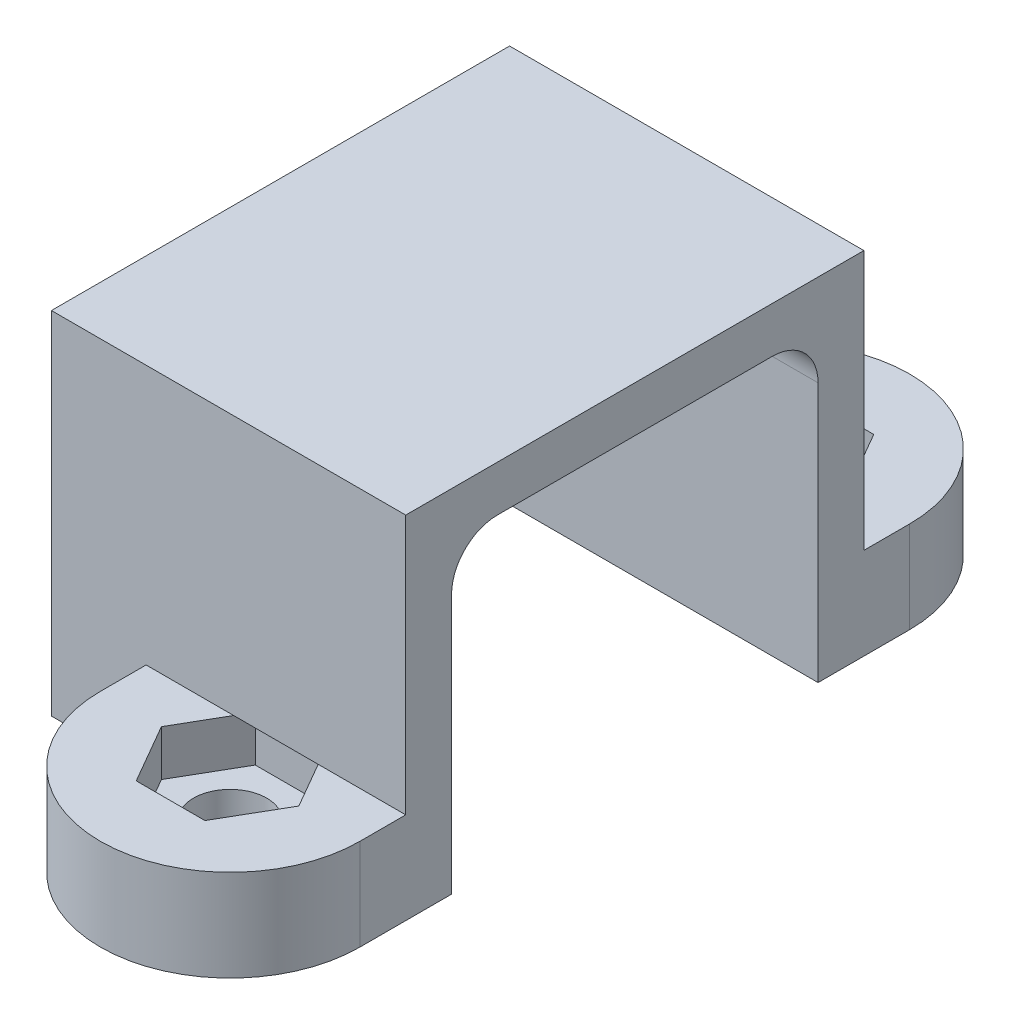
SolidWorks part; units mm, degrees
material "ABS PC"
ref_plane "Front Plane" through (0, 0, 0) normal (0, 0, 1) x (1, 0, 0)
ref_plane "Top Plane" through (0, 0, 0) normal (0, 1, 0) x (1, 0, 0)
ref_plane "Right Plane" through (0, 0, 0) normal (1, 0, 0) x (0, 0, -1)
sketch "Sketch1" plane through (0, 0, 0) normal (0, 1, 0) x (1, 0, 0)
  line L0 (0, 7.5) -> (0, -7.5) construction
  line L1 (-7.35, 0) -> (4.25, 0) construction
  line L6 (-7.35, 7.5) -> (4.25, 7.5)
  line L7 (-7.35, 7.5) -> (-7.35, -7.5)
  line L8 (-7.35, -7.5) -> (4.25, -7.5)
  line L9 (4.25, 7.5) -> (4.25, -7.5)
  line L10 (-7.35, 7.5) -> (4.25, -7.5) construction
  line L11 (-7.35, -7.5) -> (4.25, 7.5) construction
  point P3 (-1.55, 0)
  dimension "D1" = 11.6
  dimension "D2" = 15
  dimension "D3" = 4.25
extrude "body" add sketch "Sketch1" along normal blind 11.5
sketch "Sketch2" plane through (0, 0, 0) normal (0, 1, 0) x (1, 0, 0)
  line L0 (-7.35, 0) -> (4.25, 0) construction
  line L1 (-7.35, 7.5) -> (-7.35, -7.5) construction
  line L2 (4.25, -7.5) -> (4.25, 7.5) construction
  line L3 (0, 7.5) -> (0, -7.5) construction
  line L4 (4.25, 7.5) -> (-7.35, 7.5) construction
  line L5 (-7.35, -7.5) -> (4.25, -7.5) construction
  line L6 (-4.25, 9) -> (-4.25, 7.5)
  line L11 (4.25, -7.5) -> (4.25, -9)
  line L12 (-4.25, -7.5) -> (4.25, -7.5)
  line L13 (-4.25, 7.5) -> (4.25, 7.5)
  line L14 (4.25, 7.5) -> (4.25, 9)
  line L15 (-4.25, -9) -> (-4.25, -7.5)
  arc A0 (-4.25, 9) -> (4.25, 9) centre (0, 9) cw
  arc A1 (-4.25, -9) -> (4.25, -9) centre (0, -9) ccw
  dimension "D1" = 8.5
  dimension "D2" = 18
extrude "flange" add sketch "Sketch2" along normal blind 3
ref_plane "MotorFace" through (-4.05, 0, 0) normal (1, 0, 0) x (0, 0, -1)
ref_axis "AX-bolt" through (0, 3, -9) along (0, -1, 0)
ref_axis "AX-bolt2" through (0, 3, 9) along (0, -1, 0)
sketch "Sketch5" plane through (0, 0, 0) normal (0, 1, 0) x (1, 0, 0)
  line L0 (4.25, 7.5) -> (-7.35, 7.5) construction
  line L1 (2.25, 9) -> (1.125, 10.9486)
  line L2 (1.125, 10.9486) -> (-1.125, 10.9486)
  line L3 (-1.125, 10.9486) -> (-2.25, 9)
  line L4 (-2.25, 9) -> (-1.125, 7.0514)
  line L5 (-1.125, 7.0514) -> (1.125, 7.0514)
  line L6 (1.125, 7.0514) -> (2.25, 9)
  line L8 (2.25, -9) -> (1.125, -7.0514)
  line L9 (1.125, -7.0514) -> (-1.125, -7.0514)
  line L10 (-1.125, -7.0514) -> (-2.25, -9)
  line L11 (-2.25, -9) -> (-1.125, -10.9486)
  line L12 (-1.125, -10.9486) -> (1.125, -10.9486)
  line L13 (1.125, -10.9486) -> (2.25, -9)
  circle A0 centre (0, 9) radius 1.9486 construction
  circle A1 centre (0, -9) radius 1.9486 construction
  dimension "D1" = 4.5
extrude "holder-nut" cut sketch "Sketch5" against normal blind 1.5 from surface starting at face at (0, 3, -9.3125)
sketch "Sketch8" plane through (0, 0, 0) normal (0, 1, 0) x (1, 0, 0)
  circle A0 centre (0, 9) radius 1.2
  circle A1 centre (0, -9) radius 1.2
  dimension "D1" = 2.4
extrude "hole-M2" cut sketch "Sketch8" against normal through all and the other way through all
sketch "Sketch7" plane through (0, 0, 0) normal (1, 0, 0) x (0, 0, -1)
  line L0 (-9, 0) -> (9, 0) construction
  line L1 (-4.5, 10) -> (4.5, 10)
  line L2 (-6, 8.5) -> (-6, 0)
  line L3 (-6, 0) -> (6, 0)
  line L4 (6, 8.5) -> (6, 0)
  line L5 (0, 0) -> (0, 11.5) construction
  line L6 (-7.5, 11.5) -> (7.5, 11.5) construction
  line L7 (7.5, 11.5) -> (7.5, 3) construction
  arc A0 (6, 8.5) -> (4.5, 10) centre (4.5, 8.5) ccw
  arc A1 (-4.5, 10) -> (-6, 8.5) centre (-4.5, 8.5) ccw
  dimension "D3" = 1.5
  dimension "D1" = 1.5
  dimension "D2" = 1.5
extrude "fixture-motor" cut sketch "Sketch7" against normal through all both and the other way through all
sketch "Sketch9" plane through (4.25, 0, 0) normal (1, 0, 0) x (0, 0, -1)
  line L0 (-6, 8.5) -> (-6, 10)
  line L1 (-6, 10) -> (-4.5, 10)
  line L2 (4.5, 10) -> (6, 10)
  line L3 (6, 10) -> (6, 8.5)
  line L12 (6, 8.5) -> (6, 0)
  line L13 (6, 0) -> (9, 0)
  line L14 (9, 0) -> (9, 3)
  line L15 (9, 3) -> (7.5, 3)
  line L16 (7.5, 3) -> (7.5, 11.5)
  line L17 (7.5, 11.5) -> (-7.5, 11.5)
  line L18 (-7.5, 11.5) -> (-7.5, 3)
  line L19 (-7.5, 3) -> (-9, 3)
  line L20 (-9, 3) -> (-9, 0)
  line L21 (-9, 0) -> (-6, 0)
  line L22 (-6, 0) -> (-6, 8.5)
  line L23 (-4.5, 10) -> (4.5, 10)
  arc A2 (6, 8.5) -> (4.5, 10) centre (4.5, 8.5) ccw
  arc A3 (-4.5, 10) -> (-6, 8.5) centre (-4.5, 8.5) ccw
  arc A4 (6, 8.5) -> (4.5, 10) centre (4.5, 8.5) ccw
  arc A5 (-4.5, 10) -> (-6, 8.5) centre (-4.5, 8.5) ccw
  dimension "D1" = 0
extrude "gearbox-notches" cut sketch "Sketch9" against normal blind 0.8 from surface starting at plane "MotorFace"
